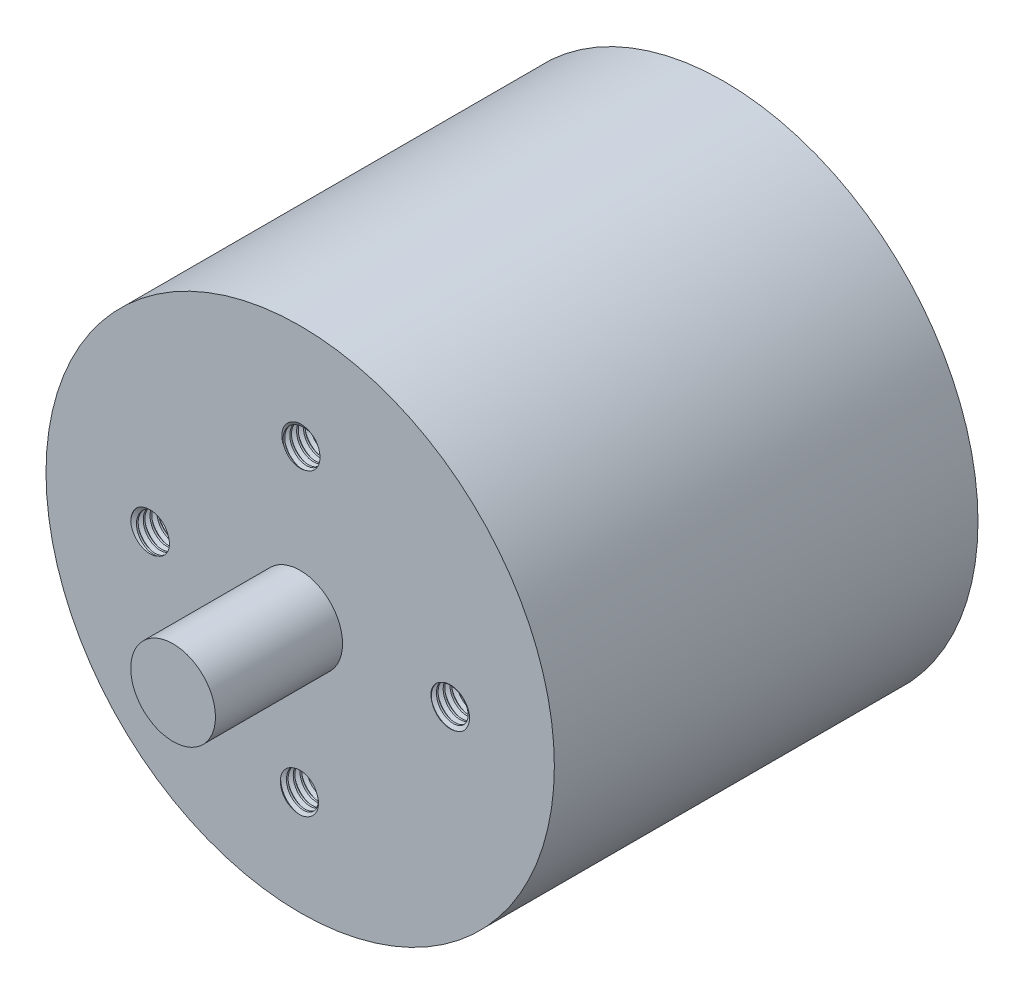
SolidWorks part; units mm, degrees
ref_plane "Front Plane" through (0, 0, 0) normal (0, 0, 1) x (1, 0, 0)
ref_plane "Top Plane" through (0, 0, 0) normal (0, 1, 0) x (1, 0, 0)
ref_plane "Right Plane" through (0, 0, 0) normal (1, 0, 0) x (0, 0, -1)
sketch "Sketch1" plane through (0, 0, 0) normal (0, 0, 1) x (1, 0, 0)
  circle A0 centre (0, 0) radius 30
  dimension "D1" = 60
extrude "Boss-Extrude1" add sketch "Sketch1" along normal blind 50
sketch "Sketch2" plane through (0, 0, 50) normal (0, 0, 1) x (1, 0, 0)
  circle A0 centre (0, 0) radius 5
  dimension "D1" = 10
extrude "Boss-Extrude2" add sketch "Sketch2" along normal blind 15
sketch "Sketch3" plane through (0, 0, 50) normal (0, 0, 1) x (1, 0, 0)
  line L0 (0, 30) -> (0, 17.5) construction
  line L1 (35.9958, 0) -> (17.5, 0) construction
  line L8 (15, 0) -> (-15, 0) construction
  line L9 (-17.5, 0) -> (-33.8675, 0) construction
  line L10 (0, -20) -> (0, -34.9606) construction
  circle A0 centre (0, 0) radius 30 construction
  circle A1 centre (0, 17.5) radius 2.5
  circle A2 centre (17.5, 0) radius 2.5
  circle A3 centre (0, -17.5) radius 2.5
  circle A4 centre (-17.5, 0) radius 2.5
  dimension "D1" = 5
  dimension "D2" = 17.5
extrude "Cut-Extrude1" cut sketch "Sketch3" against normal blind 5
thread "Thread1" pitch 0.8 method extrude profile "Thread Profile1" start angle 0, offset 1, length 6, pitch 0.8, diameter 5
ref_plane "Plane1" through (-2.5, 17.5, 51) normal (0, -1, 0) x (-1, 0, 0)
sketch "Thread Profile1" plane through (-2.5, 17.5, 51) normal (0, -1, 0) x (-1, 0, 0)
  line L0 (0, 0) -> (0, 0.8) construction
  line L11 (0, 0) -> (0, 0.7)
  line L12 (0, 0.7) -> (-0.433, 0.45)
  line L13 (-0.433, 0.45) -> (-0.433, 0.25)
  line L15 (-0.433, 0.25) -> (0, 0)
  line L17 (-0.433, 0.35) -> (0, 0.35) construction
  point P2 (0, 0)
  dimension "Pitch" = 0.8
  dimension "Profile_Angle" = 60
  dimension "Profile_Land" = 0.2
  dimension "Profile_Height" = 0.433
pattern_circular "CirPattern1" count 4 over 360 about axis through (0, 0, 50) along (0, 0, 1) of "Thread1"
sketch "Sketch9" plane through (0, 0, 50) normal (0, 0, 1) x (1, 0, 0)
  circle A0 centre (0, 0) radius 10.5241
  circle A1 centre (0, 0) radius 30
extrude "Cut-Extrude2" cut sketch "Sketch9" along normal blind 5
